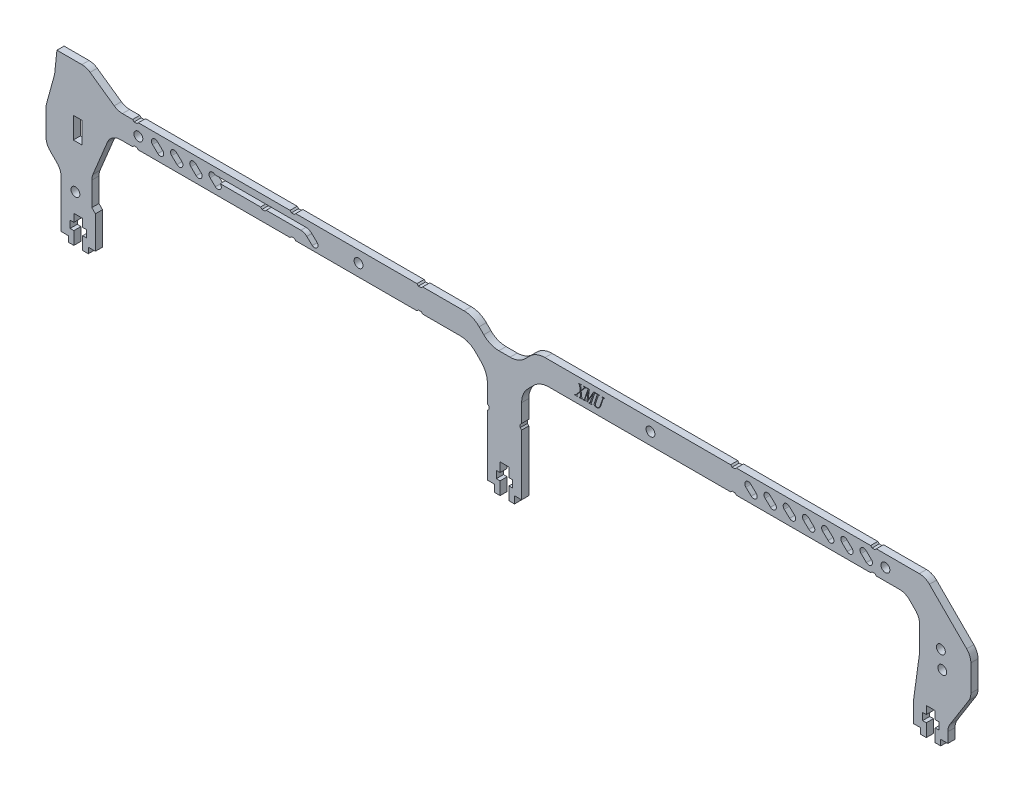
SolidWorks part; units mm, degrees
material "PPS"
ref_plane "前视基准面" through (0, 0, 0) normal (0, 0, 1) x (1, 0, 0)
ref_plane "上视基准面" through (0, 0, 0) normal (0, 1, 0) x (1, 0, 0)
ref_plane "右视基准面" through (0, 0, 0) normal (1, 0, 0) x (0, 0, -1)
sketch "草图1" plane through (0, 0, 0) normal (0, 0, 1) x (1, 0, 0)
  line L0 (-1000, 0) -> (49000, 0) construction
  line L1 (0, 0) -> (0, -218.3822) construction
  line L2 (6, -16.1697) -> (6, -48.75)
  line L3 (6, -48.75) -> (-6, -48.75) construction
  line L4 (-6, -16.1697) -> (-6, -48.75)
  line L5 (6, -48.75) -> (3.5, -48.75)
  line L6 (3.5, -48.75) -> (3.5, -51.25)
  line L7 (3.5, -51.25) -> (-3.5, -51.25) construction
  line L8 (-3.5, -48.75) -> (-3.5, -51.25)
  line L9 (-3.5, -48.75) -> (-6, -48.75)
  line L10 (1.55, -51.25) -> (1.55, -46.75)
  line L11 (1.55, -46.75) -> (2.85, -46.75)
  line L12 (2.85, -46.75) -> (2.85, -44.25)
  line L13 (2.85, -44.25) -> (1.55, -44.25)
  line L14 (1.55, -44.25) -> (1.55, -41)
  line L15 (1.55, -41) -> (-1.55, -41)
  line L16 (-1.55, -44.25) -> (-1.55, -41)
  line L17 (-2.85, -44.25) -> (-1.55, -44.25)
  line L18 (-2.85, -46.75) -> (-2.85, -44.25)
  line L19 (-1.55, -46.75) -> (-2.85, -46.75)
  line L20 (-1.55, -51.25) -> (-1.55, -46.75)
  line L21 (1.55, -51.25) -> (3.5, -51.25)
  line L22 (-1.55, -51.25) -> (-3.5, -51.25)
  line L23 (12.4197, -9.75) -> (6, -16.1697)
  line L24 (-12.4197, -9.75) -> (-6, -16.1697)
  line L25 (-147.7, -50) -> (-147.7, -45.5)
  line L26 (-150.8, -50) -> (-150.8, -45.5)
  line L27 (-147.7, -45.5) -> (-146.4, -45.5)
  line L28 (-146.4, -45.5) -> (-146.4, -43)
  line L29 (-146.4, -43) -> (-147.7, -43)
  line L30 (-147.7, -43) -> (-147.7, -40.25)
  line L31 (-150.8, -40.25) -> (-147.7, -40.25)
  line L32 (-150.8, -43) -> (-150.8, -40.25)
  line L33 (-152.1, -43) -> (-150.8, -43)
  line L34 (-152.1, -45.5) -> (-152.1, -43)
  line L35 (-150.8, -45.5) -> (-152.1, -45.5)
  line L36 (-5.0685, -7.5) -> (5.0685, -7.5)
  line L37 (5.0685, -7.5) -> (11.0685, -1.5)
  line L38 (11.0685, -1.5) -> (147.3211, -1.5)
  line L40 (145.3337, -25.5065) -> (145.3337, -14.709)
  line L41 (140.3747, -9.75) -> (12.4197, -9.75)
  line L42 (-5.0685, -7.5) -> (-11.0685, -1.5)
  line L44 (-11.0685, -1.5) -> (-157.5351, -1.5) construction
  line L45 (-137.7768, -9.75) -> (-12.4197, -9.75)
  line L50 (143.25, -40.6806) -> (143.25, -48)
  line L52 (155.25, -48) -> (143.25, -48) construction
  line L53 (155.25, -48) -> (152.75, -48)
  line L54 (152.75, -48) -> (152.75, -50)
  line L55 (152.75, -50) -> (145.75, -50) construction
  line L56 (145.75, -48) -> (145.75, -50)
  line L57 (145.75, -48) -> (143.25, -48)
  line L58 (150.8, -50) -> (150.8, -45.5)
  line L59 (150.8, -45.5) -> (152.1, -45.5)
  line L60 (152.1, -45.5) -> (152.1, -43)
  line L61 (152.1, -43) -> (150.8, -43)
  line L62 (150.8, -43) -> (150.8, -40.25)
  line L63 (150.8, -40.25) -> (147.7, -40.25)
  line L64 (147.7, -43) -> (147.7, -40.25)
  line L65 (146.4, -43) -> (147.7, -43)
  line L66 (146.4, -45.5) -> (146.4, -43)
  line L67 (147.7, -45.5) -> (146.4, -45.5)
  line L68 (147.7, -50) -> (147.7, -45.5)
  line L69 (150.8, -50) -> (152.75, -50)
  line L70 (147.7, -50) -> (145.75, -50)
  line L72 (57.6009, -1) -> (44.6221, -1) construction
  line L73 (145.3337, -25.5065) -> (143.25, -40.6806)
  line L74 (-147.7, -50) -> (-145.75, -50)
  line L75 (-150.8, -50) -> (-152.75, -50)
  line L76 (-152.75, -48) -> (-152.75, -50)
  line L77 (-155.25, -48) -> (-152.75, -48)
  line L78 (-145.75, -48) -> (-145.75, -50)
  line L79 (-145.75, -48) -> (-143.25, -48)
  line L80 (-157.5351, -1.5) -> (-160.547, -12.4412)
  line L81 (-160.547, -12.4412) -> (-160.547, -24.059)
  line L82 (-160.547, -24.059) -> (-155.25, -29.3373)
  line L87 (-143.25, -36.6226) -> (-144.5, -35.377)
  line L88 (-144.5, -35.377) -> (-144.5, -26.0402)
  line L89 (-144.5, -26.0402) -> (-137.7768, -9.75)
  line L90 (-155.25, -29.3373) -> (-155.25, -48)
  line L91 (-143.25, -36.6226) -> (-143.25, -48)
  line L92 (147.3211, -1.5) -> (163.2977, -17.4767)
  line L93 (163.2977, -17.4767) -> (163.2977, -30.1638)
  line L94 (163.2977, -30.1638) -> (155.25, -43)
  line L95 (155.25, -43) -> (155.25, -48)
  line L96 (-157.5351, -1.5) -> (-156.7241, 6.25)
  line L97 (-156.7241, 6.25) -> (-146.4, 6.25)
  line L98 (-146.4, 6.25) -> (-135.37, -1.5)
  line L99 (-135.37, -1.5) -> (-11.0685, -1.5)
  line L102 (140.3747, -9.75) -> (145.3337, -14.709)
  line L103 (56.6009, -9.75) -> (45.6221, -9.75) construction
  line L104 (146.1658, -18.25) -> (92.972, -18.25) construction
  line L105 (-154.7028, -11.25) -> (-130.7962, -11.25) construction
  circle A0 centre (-51.1115, -5.5) radius 1.55
  circle A1 centre (51.1115, -5.5) radius 1.55
  circle A5 centre (-51.1115, -5.5) radius 1.9051 construction
  circle A6 centre (51.1115, -5.5) radius 2.165 construction
  point P6 (0, -48.75)
  point P11 (0, -51.25)
  point P20 (0, -41)
  point P29 (-149.25, -40.25)
  point P43 (152.75, -49)
  point P78 (149.25, -40.25)
  dimension "D21" = 3.1
  dimension "D1" = 3.5
  dimension "D2" = 4.5
  dimension "D3" = 2.5
  dimension "D4" = 6
  dimension "D5" = 135
  dimension "D6" = 2.5
  dimension "D7" = 48.75
  dimension "D8" = 29.75
  dimension "D9" = 2
  dimension "D10" = 7
  dimension "D11" = 149.25
  dimension "D12" = 1.95
  dimension "D13" = 1.55
  dimension "D14" = 2.85
  dimension "D15" = 10.25
  dimension "D16" = 0.5
  dimension "D17" = 2.25
  dimension "D18" = 135
  dimension "D19" = 135
  dimension "D20" = 1.25
  dimension "D22" = 17.5
extrude "凸台-拉伸1" add sketch "草图1" along normal blind 2.5
sketch "草图2" plane through (0, 0, 0) normal (0, 0, 1) x (1, 0, 0)
  line L0 (98.8244, -4.7341) -> (98.8244, -1.5) construction
  line L2 (147.3211, -1.5) -> (11.0685, -1.5) construction
  line L4 (100.6889, -6.5159) -> (100.6889, -9.75) construction
  line L7 (12.4197, -9.75) -> (140.3747, -9.75) construction
  line L8 (94.8107, -5.6378) -> (97.9607, -5.6378) construction
  line L11 (86.3905, -7.4197) -> (84.526, -5.6378)
  line L16 (121.7047, -5.6122) -> (124.8547, -5.6122) construction
  line L17 (106.5671, -7.394) -> (104.7026, -5.6122)
  line L18 (104.7026, -5.6122) -> (106.4054, -3.8303) construction
  line L19 (106.4054, -3.8303) -> (108.27, -5.6122)
  line L20 (108.27, -5.6122) -> (106.5671, -7.394) construction
  line L21 (99.8252, -7.4197) -> (97.9607, -5.6378)
  line L22 (99.6881, -3.8303) -> (101.5526, -5.6122)
  line L23 (101.5526, -5.6122) -> (104.7026, -5.6122) construction
  line L24 (108.27, -5.6122) -> (111.42, -5.6122) construction
  line L25 (113.2845, -7.394) -> (111.42, -5.6122)
  line L26 (113.1228, -3.8303) -> (114.9873, -5.6122)
  line L27 (114.9873, -5.6122) -> (118.1373, -5.6122) construction
  line L28 (120.0018, -7.394) -> (118.1373, -5.6122)
  line L29 (119.8402, -3.8303) -> (121.7047, -5.6122)
  line L30 (126.7192, -7.394) -> (124.8547, -5.6122)
  line L31 (126.5819, -3.8048) -> (128.4464, -5.5866)
  line L32 (86.2289, -3.856) -> (88.0934, -5.6378)
  line L33 (88.0934, -5.6378) -> (91.2434, -5.6378) construction
  line L34 (93.1079, -7.4197) -> (91.2434, -5.6378)
  line L35 (92.9462, -3.856) -> (94.8107, -5.6378)
  line L36 (-106.2679, -5.6378) -> (-103.1179, -5.6378) construction
  line L38 (-112.9852, -5.6378) -> (-109.8352, -5.6378) construction
  line L39 (-121.4054, -7.4197) -> (-123.27, -5.6378)
  line L42 (-107.9707, -7.4197) -> (-109.8352, -5.6378)
  line L44 (-108.1324, -3.856) -> (-106.2679, -5.6378)
  line L47 (-101.2387, -7.4197) -> (-103.1032, -5.6378)
  line L48 (-101.4003, -3.856) -> (-99.5358, -5.6378) construction
  line L51 (-101.4003, -3.856) -> (-69.6149, -3.856)
  line L56 (-121.5671, -3.856) -> (-119.7026, -5.6378)
  line L57 (-119.7026, -5.6378) -> (-116.5526, -5.6378) construction
  line L58 (-114.6881, -7.4197) -> (-116.5526, -5.6378)
  line L59 (-114.8498, -3.856) -> (-112.9852, -5.6378)
  line L60 (-71.3031, -5.6378) -> (-99.5358, -5.6378)
  line L66 (-67.5422, -4.6871) -> (-65.6228, -6.5214)
  line L69 (-67.311, -8.3033) -> (-69.2304, -6.469)
  arc A10 (126.5819, -3.8048) -> (124.8547, -5.6122) centre (125.7183, -4.7085) ccw
  arc A11 (128.4464, -5.5866) -> (126.7192, -7.394) centre (127.5828, -6.4903) cw
  arc A12 (106.4054, -3.8303) -> (104.7026, -5.6122) centre (105.554, -4.7213) ccw
  arc A13 (108.27, -5.6122) -> (106.5671, -7.394) centre (107.4185, -6.5031) cw
  arc A14 (99.6881, -3.8303) -> (97.9607, -5.6378) centre (98.8244, -4.7341) ccw
  arc A15 (101.5526, -5.6122) -> (99.8252, -7.4197) centre (100.6889, -6.5159) cw
  arc A16 (113.1228, -3.8303) -> (111.42, -5.6122) centre (112.2714, -4.7213) ccw
  arc A17 (114.9873, -5.6122) -> (113.2845, -7.394) centre (114.1359, -6.5031) cw
  arc A18 (119.8402, -3.8303) -> (118.1373, -5.6122) centre (118.9887, -4.7213) ccw
  arc A19 (121.7047, -5.6122) -> (120.0018, -7.394) centre (120.8532, -6.5031) cw
  arc A20 (86.2289, -3.856) -> (84.526, -5.6378) centre (85.3774, -4.7469) ccw
  arc A21 (88.0934, -5.6378) -> (86.3905, -7.4197) centre (87.242, -6.5287) cw
  arc A22 (92.9462, -3.856) -> (91.2434, -5.6378) centre (92.0948, -4.7469) ccw
  arc A23 (94.8107, -5.6378) -> (93.1079, -7.4197) centre (93.9593, -6.5287) cw
  arc A34 (-121.5671, -3.856) -> (-123.27, -5.6378) centre (-122.4185, -4.7469) ccw
  arc A35 (-119.7026, -5.6378) -> (-121.4054, -7.4197) centre (-120.554, -6.5287) cw
  arc A36 (-114.8498, -3.856) -> (-116.5526, -5.6378) centre (-115.7012, -4.7469) ccw
  arc A37 (-112.9852, -5.6378) -> (-114.6881, -7.4197) centre (-113.8367, -6.5287) cw
  arc A38 (-108.1324, -3.856) -> (-109.8352, -5.6378) centre (-108.9838, -4.7469) ccw
  arc A39 (-106.2679, -5.6378) -> (-107.9707, -7.4197) centre (-107.1193, -6.5287) cw
  arc A40 (-101.4003, -3.856) -> (-103.1032, -5.6378) centre (-102.2518, -4.7469) ccw
  arc A41 (-99.5358, -5.6378) -> (-101.2387, -7.4197) centre (-100.3873, -6.5287) cw
  arc A46 (-71.3031, -5.6378) -> (-69.2304, -6.469) centre (-71.3031, -8.6378) cw
  arc A47 (-65.6228, -6.5214) -> (-67.311, -8.3033) centre (-66.548, -7.3355) cw
  arc A48 (-69.6149, -3.856) -> (-67.5422, -4.6871) centre (-69.6149, -6.856) cw
extrude "减重" cut sketch "草图2" against normal through all from surface starting at face at (-5.419, -35.997, 2.5)
sketch "草图5" plane through (0, 0, 0) normal (0, 0, 1) x (1, 0, 0)
  line L0 (-123.27, -5.6378) -> (-121.4054, -7.4197) construction
  line L1 (-126.42, -5.6378) -> (-123.27, -5.6378) construction
  line L2 (-126.42, -5.6378) -> (-128.2845, -3.856) construction
  line L3 (-128.1228, -7.4197) -> (-129.9873, -5.6378) construction
  line L4 (-129.1359, -4.7469) -> (-127.2714, -6.5287) construction
  line L5 (132.4479, -4.6957) -> (134.3124, -6.4776) construction
  line L9 (128.4464, -5.5866) -> (131.5964, -5.5866) construction
  line L10 (135.1638, -5.5866) -> (133.2993, -3.8048) construction
  line L11 (133.4609, -7.3685) -> (131.5964, -5.5866) construction
  arc A1 (-126.42, -5.6378) -> (-128.1228, -7.4197) centre (-127.2714, -6.5287) cw construction
  arc A2 (-129.9873, -5.6378) -> (-128.2845, -3.856) centre (-129.1359, -4.7469) cw construction
  arc A7 (135.1638, -5.5866) -> (133.4609, -7.3685) centre (134.3124, -6.4776) cw construction
  arc A8 (131.5964, -5.5866) -> (133.2993, -3.8048) centre (132.4479, -4.6957) cw construction
  circle A9 centre (-128.2036, -5.6378) radius 1.55
  circle A11 centre (133.3801, -5.5866) radius 1.55
  dimension "D1" = 3.1
extrude "光球接口" cut sketch "草图5" along normal through all
sketch "草图3" plane through (0, 0, 2.5) normal (0, 0, 1) x (1, 0, 0)
  text T0 "XMU" font "宋体" height 4.25
extrude "切除-拉伸3" cut sketch "草图3" against normal through all
sketch "草图4" plane through (0, 0, 0) normal (0, 0, 1) x (1, 0, 0)
  line L0 (-6, -25.591) -> (-5.5, -26.091)
  line L1 (-6, -16.1697) -> (-6, -48.75) construction
  line L2 (-5.5, -26.091) -> (-5.5, -27.091)
  line L3 (-5.5, -27.091) -> (-6, -27.591)
  line L4 (-6, -27.591) -> (-6, -25.591)
  line L5 (0, 0) -> (0, -67.6388) construction
  line L6 (6, -27.591) -> (6, -25.591)
  line L7 (5.5, -27.091) -> (6, -27.591)
  line L8 (5.5, -26.091) -> (5.5, -27.091)
  line L9 (6, -25.591) -> (5.5, -26.091)
  line L18 (-11.0685, -1.5) -> (-135.37, -1.5) construction
  line L19 (-128.2051, -1.5) -> (-130.2051, -1.5)
  line L20 (-128.7051, -2) -> (-128.2051, -1.5)
  line L21 (-129.7051, -2) -> (-128.7051, -2)
  line L22 (-130.2051, -1.5) -> (-129.7051, -2)
  line L23 (0, 0) -> (-134.5835, 0) construction
  line L36 (-137.7768, -9.75) -> (-12.4197, -9.75) construction
  line L41 (-99.5358, -5.6378) -> (-71.3031, -5.6378) construction
  line L46 (130.2051, -1.5) -> (129.7051, -2)
  line L47 (129.7051, -2) -> (128.7051, -2)
  line L48 (128.7051, -2) -> (128.2051, -1.5)
  line L49 (128.2051, -1.5) -> (130.2051, -1.5)
  line L50 (-135.37, -1.5) -> (-135.37, -9.75) construction
  line L51 (-1135.37, -5.625) -> (48864.63, -5.625) construction
  line L52 (-130.2051, -9.75) -> (-129.7051, -9.25)
  line L53 (-129.7051, -9.25) -> (-128.7051, -9.25)
  line L54 (-128.7051, -9.25) -> (-128.2051, -9.75)
  line L55 (-128.2051, -9.75) -> (-130.2051, -9.75)
  line L64 (-73.0982, -1.5) -> (-75.0982, -1.5)
  line L65 (-73.5982, -2) -> (-73.0982, -1.5)
  line L66 (-74.5982, -2) -> (-73.5982, -2)
  line L67 (-75.0982, -1.5) -> (-74.5982, -2)
  line L68 (-75.0982, -9.75) -> (-74.5982, -9.25)
  line L69 (-74.5982, -9.25) -> (-73.5982, -9.25)
  line L70 (-73.5982, -9.25) -> (-73.0982, -9.75)
  line L71 (-73.0982, -9.75) -> (-75.0982, -9.75)
  line L72 (-28.6523, -1.5) -> (-30.6523, -1.5)
  line L73 (-29.1523, -2) -> (-28.6523, -1.5)
  line L74 (-30.1523, -2) -> (-29.1523, -2)
  line L75 (-30.6523, -1.5) -> (-30.1523, -2)
  line L76 (-30.6523, -9.75) -> (-30.1523, -9.25)
  line L77 (-30.1523, -9.25) -> (-29.1523, -9.25)
  line L78 (-29.1523, -9.25) -> (-28.6523, -9.75)
  line L79 (-28.6523, -9.75) -> (-30.6523, -9.75)
  line L80 (-83.4194, -5.6378) -> (-85.4194, -5.6378)
  line L81 (-83.9194, -6.1378) -> (-83.4194, -5.6378)
  line L82 (-84.9194, -6.1378) -> (-83.9194, -6.1378)
  line L83 (-85.4194, -5.6378) -> (-84.9194, -6.1378)
  line L92 (79.1823, -9.75) -> (81.1823, -9.75)
  line L93 (128.2051, -9.75) -> (130.2051, -9.75)
  line L94 (128.7051, -9.25) -> (128.2051, -9.75)
  line L95 (129.7051, -9.25) -> (128.7051, -9.25)
  line L96 (130.2051, -9.75) -> (129.7051, -9.25)
  line L97 (-151, -10.625) -> (-148, -10.625)
  line L98 (-148, -10.625) -> (-148, -18.125)
  line L99 (-148, -18.125) -> (-151, -18.125)
  line L100 (-151, -18.125) -> (-151, -10.625)
  line L101 (79.6823, -9.25) -> (79.1823, -9.75)
  line L102 (80.6823, -9.25) -> (79.6823, -9.25)
  line L103 (81.1823, -9.75) -> (80.6823, -9.25)
  line L104 (81.1823, -1.5) -> (80.6823, -2)
  line L105 (80.6823, -2) -> (79.6823, -2)
  line L106 (79.6823, -2) -> (79.1948, -1.5)
  line L107 (79.1948, -1.5) -> (81.1823, -1.5)
  line L108 (147.3211, -1.5) -> (11.0685, -1.5) construction
  line L109 (163.2977, -30.1638) -> (163.2977, -17.4767) construction
  line L110 (-144.5, -35.377) -> (-144.5, -26.0402) construction
  line L112 (-155.25, -48) -> (-152.75, -48) construction
  circle A0 centre (-150.25, -33.5) radius 1.55
  circle A1 centre (152.7976, -20.675) radius 1.55
  circle A2 centre (153.2976, -26.6541) radius 1.55
  point P4 (-6, -26.591)
  point P19 (-85.4194, -5.6378)
  point P49 (-135.37, -5.625)
  dimension "D13" = 3.1
  dimension "D20" = 3.1
  dimension "D1" = 45
  dimension "D2" = 0.5
  dimension "D3" = 1
  dimension "D4" = 45
  dimension "D5" = 0.5
  dimension "D6" = 1
  dimension "D7" = 45
  dimension "D8" = 1
  dimension "D9" = 6
  dimension "D10" = 15.05
  dimension "D11" = 10.0002
  dimension "D12" = 0.5
  dimension "D14" = 5
  dimension "D15" = 7.5
  dimension "D16" = 3
  dimension "D17" = 14.5
  dimension "D18" = 3.5
  dimension "D19" = 5.75
extrude "线槽和设备接口" cut sketch "草图4" along normal through all
fillet "圆角2" radius 5 16 edges at (155.25, -43, 1.25) (145.3337, -25.5065, 1.25) (143.25, -40.6806, 1.25) (147.3211, -1.5, 1.25) (163.2977, -30.1638, 1.25) (163.2977, -17.4767, 1.25) (145.3337, -14.709, 1.25) (140.3747, -9.75, 1.25) (-137.7768, -9.75, 1.25) (-144.5, -26.0402, 1.25) (-146.4, 6.25, 1.25) (-155.25, -29.3373, 1.25) (-160.547, -24.059, 1.25) (-160.547, -12.4412, 1.25) (-157.5351, -1.5, 1.25) (-135.37, -1.5, 1.25)
fillet "圆角3" radius 7.5 8 edges at (12.4197, -9.75, 1.25) (6, -16.1697, 1.25) (-6, -16.1697, 1.25) (-12.4197, -9.75, 1.25) (11.0685, -1.5, 1.25) (5.0685, -7.5, 1.25) (-5.0685, -7.5, 1.25) (-11.0685, -1.5, 1.25)
